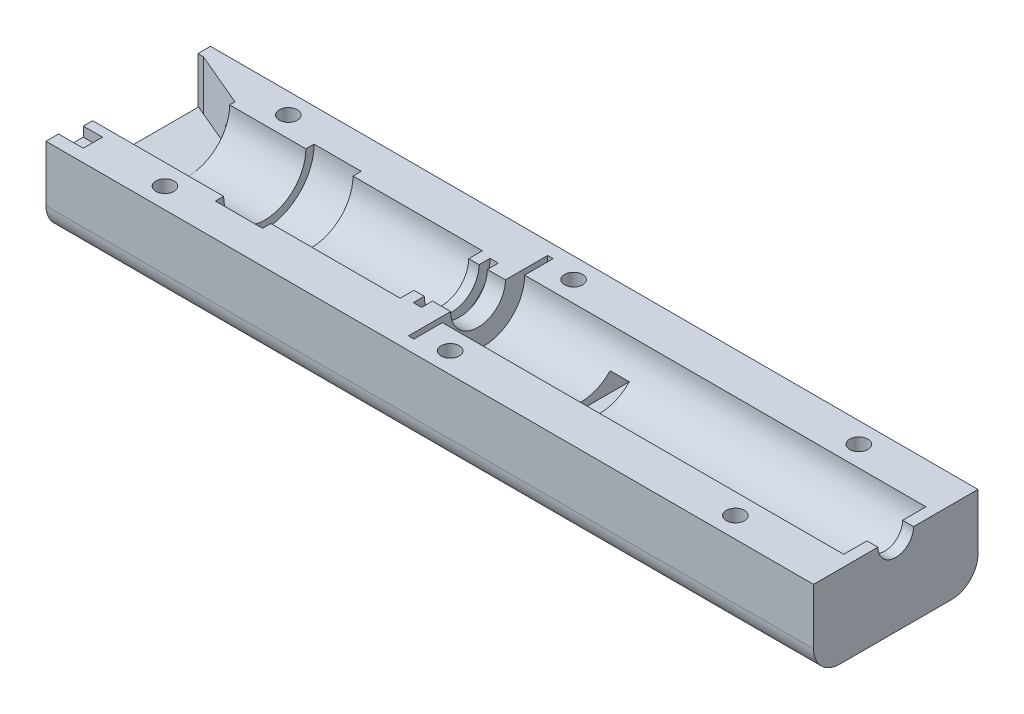
SolidWorks part; units mm, degrees
ref_plane "Front Plane" through (0, 0, 0) normal (0, 0, 1) x (1, 0, 0)
ref_plane "Top Plane" through (0, 0, 0) normal (0, 1, 0) x (1, 0, 0)
ref_plane "Right Plane" through (0, 0, 0) normal (1, 0, 0) x (0, 0, -1)
sketch "Sketch2" plane through (0, 0, 0) normal (0, 1, 0) x (1, 0, 0)
  line L0 (0, -15) -> (140, -15)
  line L1 (0, 0) -> (140, 0)
  line L2 (0, -15) -> (0, 15)
  line L3 (0, 15) -> (140, 15)
  line L4 (140, -15) -> (140, 15)
  dimension "D1" = 140
  dimension "D2" = 15
extrude "Base" add sketch "Sketch2" against normal blind 15 contours L0 L4 L1 L2 | L1 L4 L3 L2
sketch "Sketch3" plane through (0, 0, 0) normal (-1, 0, 0) x (0, 0, 1)
  circle A0 centre (0, 0) radius 7.5
  dimension "D1" = 15
extrude "Center_cut" cut sketch "Sketch3" against normal through all
sketch "Sketch4" plane through (0, 0, 0) normal (0, 1, 0) x (1, 0, 0)
  line L0 (0, 15) -> (140, 15) construction
  line L1 (0, 12.7) -> (1, 12.7)
  line L2 (0, 12.7) -> (0, -12.7)
  line L3 (0, -12.7) -> (1, -12.7)
  line L4 (1, 12.7) -> (1, -12.7)
  line L5 (0, 7.5) -> (0, 15) construction
  dimension "D1" = 25.4
  dimension "D2" = 2.3
  dimension "D3" = 0
  dimension "D4" = 1
extrude "Antenna_PCB" cut sketch "Sketch4" against normal blind 10.2
sketch "Sketch14" plane through (1, 0, 0) normal (-1, 0, 0) x (0, 0, 1)
  line L0 (12.7, 0) -> (7.5, 0) construction
  line L1 (9.2, -1.75) -> (12.7, -1.75)
  line L2 (9.2, -1.75) -> (9.2, 1.75)
  line L3 (9.2, 1.75) -> (12.7, 1.75)
  line L4 (12.7, -1.75) -> (12.7, 1.75)
  line L5 (9.2, -1.75) -> (12.7, 1.75) construction
  line L6 (9.2, 1.75) -> (12.7, -1.75) construction
  line L7 (12.7, -10.2) -> (12.7, 0) construction
  point P0 (10.95, 0)
  dimension "D1" = 3.5
  dimension "D2" = 3.5
  dimension "D3" = 0
extrude "Coaxial_connector" cut sketch "Sketch14" against normal blind 3.5
sketch "Sketch8" plane through (1, 0, 0) normal (-1, 0, 0) x (0, 0, 1)
  circle A0 centre (0, 0) radius 9
  dimension "D1" = 18
extrude "Lens" cut sketch "Sketch8" against normal blind 8.6 from offset 23.9 offset against normal yes
sketch "Sketch10" plane through (1, 0, 0) normal (-1, 0, 0) x (0, 0, 1)
  line L1 (12.7, 10.2) -> (-12.7, 10.2)
  line L2 (12.7, 10.2) -> (12.7, -10.2)
  line L3 (12.7, -10.2) -> (-12.7, -10.2)
  line L4 (-12.7, 10.2) -> (-12.7, -10.2)
  line L5 (12.7, 10.2) -> (-12.7, -10.2) construction
  line L6 (12.7, -10.2) -> (-12.7, 10.2) construction
  point P0 (0, 0)
extrude "Photodiode_PCB" cut sketch "Sketch10" against normal blind 1 from offset 62.8 offset against normal yes
fillet "Fillet1" radius 4.8 2 edges at (70, -15, 15) (70, -15, -15)
sketch "Sketch15" plane through (140, 0, 0) normal (1, 0, 0) x (0, 0, -1)
  line L0 (-11.25, 0) -> (-11.25, -14.8837) construction
  line L1 (-15, 0) -> (-7.5, 0) construction
  line L2 (7.5, 0) -> (15, 0) construction
  line L3 (11.25, 0) -> (-11.25, 0)
  line L4 (11.25, 0) -> (11.25, -8)
  line L5 (11.25, -8) -> (-11.25, -8)
  line L6 (-11.25, 0) -> (-11.25, -8)
  arc A0 (-15, -10.2) -> (-10.2, -15) centre (-10.2, -10.2) ccw construction
  arc A1 (-3.25, 0) -> (3.25, 0) centre (0, 0) ccw
  line M10 (15, 0) -> (7.5, 0)
  arc M11 (7.5, 0) -> (-7.5, 0) centre (0, 0) cw
  line M12 (-7.5, 0) -> (-15, 0)
  dimension "D2" = 3.25
  dimension "D1" = 8
extrude "Coax_connector_hole" add sketch "Sketch15" against normal blind 2 contours A1 L3 M11 | L6 L5 L4 M12 M10 M11
sketch "Sketch16" plane through (1, 0, 0) normal (-1, 0, 0) x (0, 0, 1)
  line L5 (0, -7.5) -> (-12.7, -7.5)
  line L6 (0, -7.5) -> (0, 0)
  line L7 (0, 0) -> (-12.7, 0)
  line L8 (-12.7, -7.5) -> (-12.7, 0)
  arc A0 (-7.5, 0) -> (7.5, 0) centre (0, 0) ccw construction
extrude "Cut-Extrude2" cut sketch "Sketch16" against normal blind 10
sketch "Sketch17" plane through (0, 0, 0) normal (0, 1, 0) x (1, 0, 0)
  line L0 (1, 12.7) -> (11, 8.4553)
  line L1 (11, 12.7) -> (11, 0) construction
  line L2 (11, 12.7) -> (0, 12.7) construction
  line L3 (11, 8.4553) -> (11, 12.7)
  line L4 (11, 12.7) -> (1, 12.7)
  dimension "D1" = 23
extrude "Boss-Extrude1" add sketch "Sketch17" against normal up to next
sketch "Sketch18" plane through (0, -7.5, 0) normal (0, 1, 0) x (1, 0, 0)
  line L0 (1, 12.7) -> (0.6874, 11.9636)
  line L1 (11, 8.4553) -> (10.6874, 7.7188)
  line L2 (1, 12.7) -> (11, 8.4553) construction
  line L3 (0.6874, 11.9636) -> (10.6874, 7.7188)
  line L4 (10.6874, 7.7188) -> (11, 7.5862)
  line L5 (11, 8.4553) -> (11, 0) construction
  line L6 (11, 7.5862) -> (11, 8.4553)
  line M4 (11, 8.4553) -> (1, 12.7)
  line M5 (1, 12.7) -> (1, 0)
  dimension "D1" = 0.8
  dimension "D2" = 90
  dimension "D3" = 0.8
  dimension "D4" = 90
extrude "Cut-Extrude3" cut sketch "Sketch18" against normal blind 2.7 contours L3 L1 M5 M4
sketch "Sketch19" plane through (0, 0, 0) normal (0, 1, 0) x (1, 0, 0)
  line L0 (17.95, 7.5) -> (17.95, 15) construction
  line L1 (24.9, 7.5) -> (11, 7.5) construction
  line L2 (0, 15) -> (140, 15) construction
  line L3 (122, 15) -> (122, 7.5) construction
  line L4 (138, 7.5) -> (64.8, 7.5) construction
  line L5 (140, 3.25) -> (140, 15) construction
  line L6 (17.95, 11.25) -> (122, 11.25) construction
  line L7 (11, 0) -> (1, 0) construction
  circle A0 centre (17.95, 11.25) radius 1.65
  circle A1 centre (122, 11.25) radius 1.65
  circle A2 centre (122, -11.25) radius 1.65
  circle A3 centre (17.95, -11.25) radius 1.65
  circle A4 centre (69.975, 11.25) radius 1.65
  circle A5 centre (69.975, -11.25) radius 1.65
  dimension "D2" = 3.3
  dimension "D3" = 3.3
  dimension "D4" = 3.3
  dimension "D1" = 18
extrude "Cut-Extrude4" cut sketch "Sketch19" against normal blind 15
sketch "Sketch20" plane through (0, -15, 0) normal (0, -1, 0) x (1, 0, 0)
  line L0 (0, 0) -> (140, 0) construction
  line L2 (140, 10.2) -> (140, -10.2) construction
  line L3 (70, 0) -> (70, 15) construction
  line L4 (0, 15) -> (140, 15) construction
  circle A0 centre (17.95, 11.25) radius 2.85
  circle A1 centre (122.05, 11.25) radius 2.85
  circle A2 centre (122.05, -11.25) radius 2.85
  circle A3 centre (17.95, -11.25) radius 2.85
  circle A4 centre (69.975, 11.25) radius 2.85
  circle A5 centre (69.975, -11.25) radius 2.85
  dimension "D1" = 5.7
  dimension "D2" = 5.7
extrude "Cut-Extrude5" cut sketch "Sketch20" against normal blind 1.5
sketch "Sketch21" plane through (0, 0, -15) normal (0, 0, -1) x (-1, 0, 0)
  line L0 (-140, -10.2) -> (0, -10.2) construction
  line L1 (-8, -10.2) -> (-11, -10.2)
  line L2 (-8, -10.2) -> (-8, -5.7)
  line L3 (-8, -5.7) -> (-11, -5.7)
  line L4 (-11, -10.2) -> (-11, -5.7)
  line L5 (0, -10.2) -> (0, 0) construction
  dimension "D1" = 3
  dimension "D2" = 4.5
  dimension "D3" = 11
extrude "Cut-Extrude6" cut sketch "Sketch21" against normal up to next
sketch "Sketch22" plane through (0, 0, -15) normal (0, 0, -1) x (-1, 0, 0)
  line L6 (-11, -10.2) -> (-86, -10.2)
  line L7 (-11, -10.2) -> (-11, -6.7)
  line L8 (-11, -6.7) -> (-86, -6.7)
  line L9 (-86, -10.2) -> (-86, -6.7)
  dimension "D1" = 3.5
  dimension "D2" = 75
extrude "Cut-Extrude7" cut sketch "Sketch22" against normal blind 2
sketch "Sketch24" plane through (0, 0, -15) normal (0, 0, -1) x (-1, 0, 0)
  line L6 (-86, -6.7) -> (-86, -10.2) construction
  line L7 (-86, -8.7) -> (-82.5, -8.7)
  line L8 (-86, -8.7) -> (-86, -5.2)
  line L9 (-86, -5.2) -> (-82.5, -5.2)
  line L10 (-82.5, -8.7) -> (-82.5, -5.2)
  line L11 (-140, -10.2) -> (-86, -10.2) construction
  dimension "D1" = 3.5
  dimension "D2" = 3.5
  dimension "D3" = 5
extrude "Cut-Extrude8" cut sketch "Sketch24" against normal blind 15
chamfer "Chamfer2" distance 1.5 angle 45 1 edges at (84.25, -8.7, -13)
sketch "Sketch25" plane through (1, 0, 0) normal (-1, 0, 0) x (0, 0, 1)
  line L0 (-11.8309, -7.5) -> (0, -7.5) construction
  line L1 (7.5, 0) -> (-7.5, 0)
  line L2 (7.5, 0) -> (7.5, -7.5)
  line L3 (7.5, -7.5) -> (-7.5, -7.5)
  line L4 (-7.5, 0) -> (-7.5, -7.5)
  line L5 (-7.5862, -7.5) -> (0, -7.5) construction
  arc A0 (-5, 0) -> (5, 0) centre (0, 0) ccw
  line M2 (0, -7.5) -> (-11.8309, -7.5)
  arc M9 (7.5, 0) -> (0, -7.5) centre (0, 0) cw
  dimension "D2" = 5
  dimension "D1" = 15
extrude "Filter_mount" add sketch "Sketch25" against normal blind 6.7 from offset 56.1 contours A0 L1 L4 M2 M9 | L3 L2 M9 offset against normal yes
sketch "Sketch9" plane through (1, 0, 0) normal (-1, 0, 0) x (0, 0, 1)
  circle A0 centre (0, 0) radius 7
  dimension "D1" = 14
extrude "Filter_space" cut sketch "Sketch9" against normal blind 1.5 from offset 58
